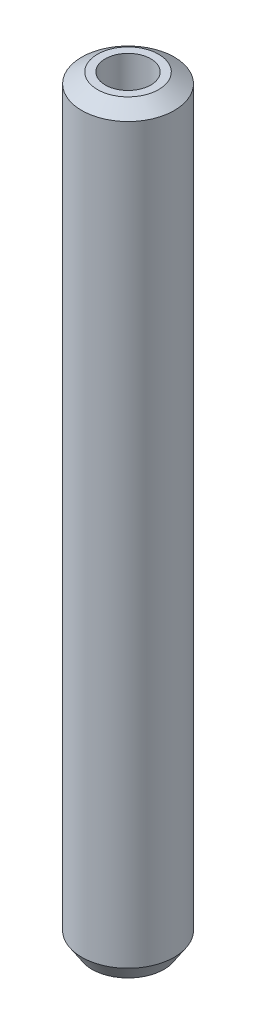
SolidWorks part; units mm, degrees
ref_plane "Front Plane" through (0, 0, 0) normal (0, 0, 1) x (1, 0, 0)
ref_plane "Top Plane" through (0, 0, 0) normal (0, 1, 0) x (1, 0, 0)
ref_plane "Right Plane" through (0, 0, 0) normal (1, 0, 0) x (0, 0, -1)
sketch "Sketch1" plane through (0, 0, 0) normal (0, 1, 0) x (1, 0, 0)
  circle A0 centre (0, 0) radius 20
  dimension "SHAFT_OD" = 40
extrude "Boss-Extrude1" add sketch "Sketch1" along normal blind 327.9911
sketch "Sketch2" plane through (0, 0, 0) normal (0, 1, 0) x (1, 0, 0)
  circle A0 centre (0, 0) radius 9.8321
  dimension "BORE_D" = 19.6642
extrude "Cut-Extrude1" cut sketch "Sketch2" along normal through all
chamfer "Chamfer1" distance 4.4344 angle 56.792 2 edges at (0, 327.9911, 20) (0, 0, 20) first distance on face at (0, 327.9911, 20) first distance on face at (0, 0, 9.8321)
